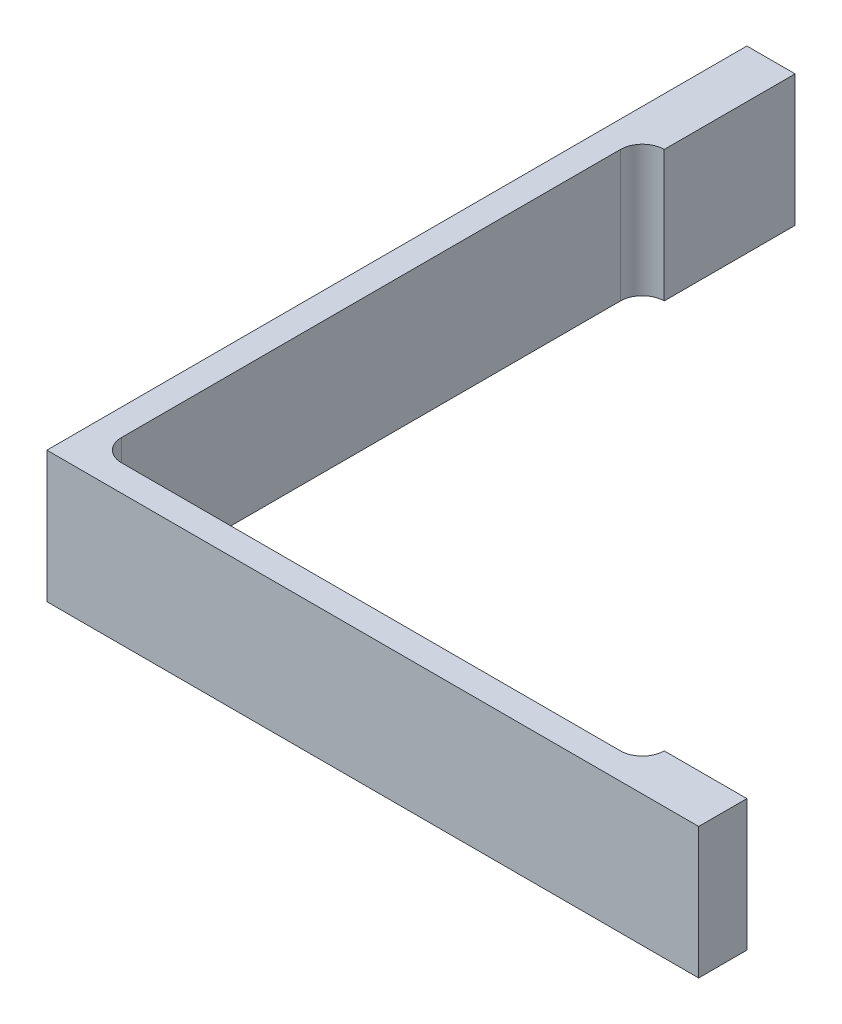
SolidWorks part; units mm, degrees
ref_plane "Front Plane" through (0, 0, 0) normal (0, 0, 1) x (1, 0, 0)
ref_plane "Top Plane" through (0, 0, 0) normal (0, 1, 0) x (1, 0, 0)
ref_plane "Right Plane" through (0, 0, 0) normal (1, 0, 0) x (0, 0, -1)
sketch "Sketch1" plane through (0, 0, 0) normal (0, 1, 0) x (1, 0, 0)
  line L0 (0, 0) -> (0, 50.8)
  line L2 (3.5, 50.8) -> (3.5, 3.5)
  line L3 (3.5, 3.5) -> (47.3, 3.5)
  line L5 (47.3, 0) -> (0, 0)
  line L6 (0, 50.8) -> (3.5, 50.8)
  line L7 (47.3, 0) -> (47.3, 3.5)
  point P3 (0, 0)
  point P4 (3.5, 50.8)
  point P6 (50.8, 0)
  dimension "D1" = 3.5
  dimension "D2" = 50.8
  dimension "D3" = 47.3
  dimension "D5" = 3.5
extrude "Boss-Extrude1" add sketch "Sketch1" along normal blind 9.525
sketch "Sketch2" plane through (0, 9.525, 0) normal (0, 1, 0) x (1, 0, 0)
  line L0 (3.5, 3.5) -> (3.5, 50.8) construction
  line L1 (3.5, 41.3) -> (1.9125, 41.3)
  line L2 (3.5, 41.3) -> (3.5, 3.5)
  line L4 (1.9125, 41.3) -> (1.9125, 3.5)
  line L5 (47.3, 3.5) -> (3.5, 3.5) construction
  line L6 (3.5, 3.5) -> (41.3, 3.5)
  line L7 (1.9125, 3.5) -> (1.9125, 1.9125)
  line L8 (1.9125, 1.9125) -> (41.3, 1.9125)
  line L9 (41.3, 3.5) -> (41.3, 1.9125)
  point P12 (3.5, 3.5)
  point P16 (2.259, 3.5)
  dimension "D1" = 9.5
  dimension "D4" = 6
  dimension "D5" = 1.5875
extrude "Cut-Extrude1" cut sketch "Sketch2" against normal through all
fillet "Fillet1" radius 1.5875 3 edges at (41.3, 4.7625, -1.9125) (1.9125, 4.7625, -1.9125) (1.9125, 4.7625, -41.3)
